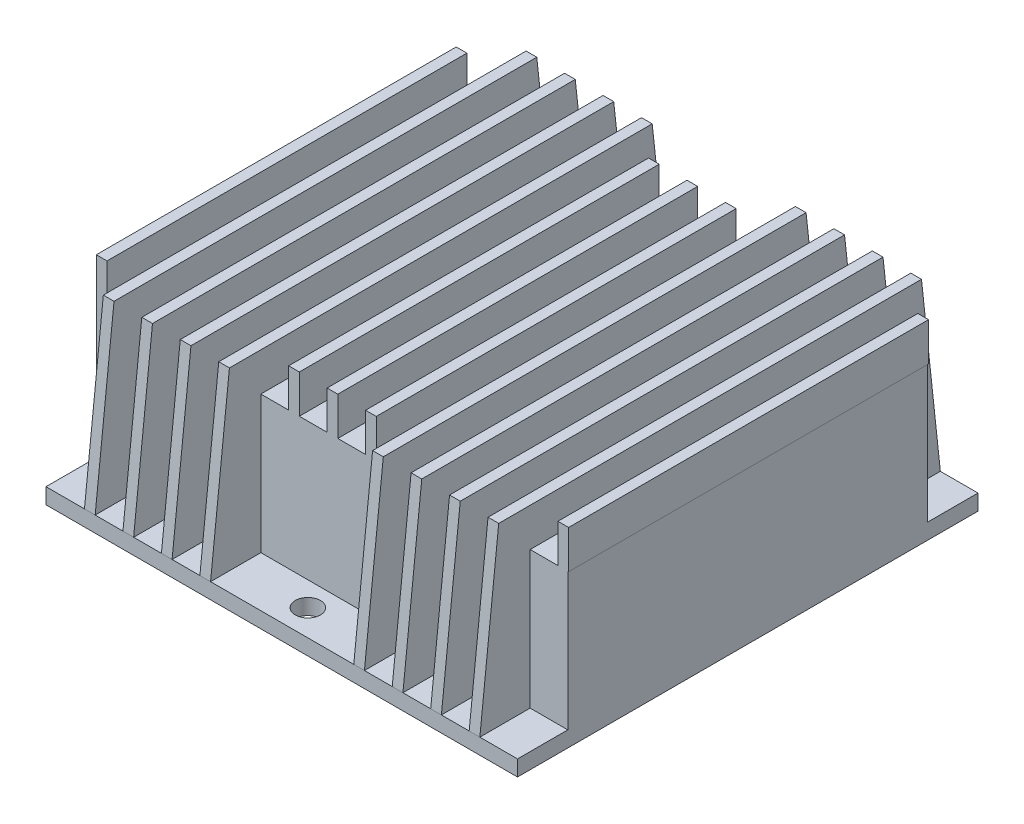
SolidWorks part; units mm, degrees
ref_plane "Front Plane" through (0, 0, 0) normal (0, 0, 1) x (1, 0, 0)
ref_plane "Top Plane" through (0, 0, 0) normal (0, 1, 0) x (1, 0, 0)
ref_plane "Right Plane" through (0, 0, 0) normal (1, 0, 0) x (0, 0, -1)
sketch "Sketch1" plane through (0, 0, 0) normal (0, 1, 0) x (1, 0, 0)
  line L1 (37.5, -36.625) -> (-37.5, -36.625)
  line L2 (37.5, -36.625) -> (37.5, 36.625)
  line L3 (37.5, 36.625) -> (-37.5, 36.625)
  line L4 (-37.5, -36.625) -> (-37.5, 36.625)
  line L5 (37.5, -36.625) -> (-37.5, 36.625) construction
  line L6 (37.5, 36.625) -> (-37.5, -36.625) construction
  point P0 (0, 0)
  dimension "D1" = 75
  dimension "D2" = 73.25
extrude "Boss-Extrude1" add sketch "Sketch1" along normal blind 2.5
sketch "Sketch2" plane through (0, 2.5, 0) normal (0, 1, 0) x (1, 0, 0)
  line L0 (-37.5, 36.625) -> (-37.5, -36.625) construction
  line L1 (37.5, -28.625) -> (-37.5, -28.625)
  line L2 (37.5, -28.625) -> (37.5, 28.625)
  line L3 (37.5, 28.625) -> (-37.5, 28.625)
  line L4 (-37.5, -28.625) -> (-37.5, 28.625)
  line L5 (37.5, -28.625) -> (-37.5, 28.625) construction
  line L6 (37.5, 28.625) -> (-37.5, -28.625) construction
  line L7 (37.5, 36.625) -> (-37.5, 36.625) construction
  point P0 (0, 0)
  dimension "D1" = 8
extrude "Boss-Extrude2" add sketch "Sketch2" along normal blind 21.85
sketch "Sketch3" plane through (-37.5, 0, 0) normal (-1, 0, 0) x (0, 0, 1)
  line L0 (-33.625, 30.45) -> (33.625, 30.45)
  line L1 (-28.625, 24.35) -> (28.625, 24.35) construction
  line L2 (-28.625, 24.35) -> (-28.625, 2.5) construction
  line L3 (28.625, 24.35) -> (28.625, 2.5) construction
  line L4 (-33.625, 30.45) -> (-36.625, 2.5)
  line L5 (-36.625, 2.5) -> (-28.625, 2.5)
  line L6 (-28.625, 2.5) -> (-28.625, 24.35)
  line L7 (-28.625, 24.35) -> (28.625, 24.35)
  line L8 (28.625, 24.35) -> (28.625, 2.5)
  line L9 (28.625, 2.5) -> (36.625, 2.5)
  line L10 (36.625, 2.5) -> (33.625, 30.45)
  dimension "D1" = 6.1
  dimension "D2" = 5
  dimension "D3" = 5
extrude "Boss-Extrude3" add sketch "Sketch3" against normal blind 1.7
pattern_linear "LPattern1" count 13 spacing 6.1192 along (1, 0, 0) of "Boss-Extrude3"
sketch "Sketch4" plane through (0, 24.35, 0) normal (0, 1, 0) x (1, 0, 0)
  line L1 (-35.8, -28.625) -> (-37.5, -28.625)
  line L2 (-35.8, -28.625) -> (-35.8, -36.625)
  line L3 (-35.8, -36.625) -> (-37.5, -36.625)
  line L4 (-37.5, -28.625) -> (-37.5, -36.625)
  line L9 (-5.2038, -36.625) -> (-0.7846, -36.625) construction
  line L10 (-6.9038, -28.625) -> (-5.2038, -28.625)
  line L11 (-6.9038, -28.625) -> (-6.9038, -36.625)
  line L12 (-6.9038, -36.625) -> (-5.2038, -36.625)
  line L13 (-5.2038, -28.625) -> (-5.2038, -36.625)
  line L14 (-5.2038, -28.625) -> (-5.2038, -36.625) construction
  line L16 (-0.7846, -28.625) -> (0.9154, -28.625)
  line L17 (-0.7846, -28.625) -> (-0.7846, -36.625)
  line L18 (-0.7846, -36.625) -> (0.9154, -36.625)
  line L19 (0.9154, -28.625) -> (0.9154, -36.625)
  line L20 (5.3346, -28.625) -> (7.0346, -28.625)
  line L21 (5.3346, -28.625) -> (5.3346, -36.625)
  line L22 (5.3346, -36.625) -> (7.0346, -36.625)
  line L23 (7.0346, -28.625) -> (7.0346, -36.625)
  line L24 (35.9308, -28.625) -> (37.6308, -28.625)
  line L25 (35.9308, -28.625) -> (35.9308, -36.625)
  line L26 (35.9308, -36.625) -> (37.6308, -36.625)
  line L27 (37.6308, -28.625) -> (37.6308, -36.625)
  line L28 (-37.5, 28.625) -> (-35.8, 28.625)
  line L29 (-37.5, 28.625) -> (-37.5, 36.625)
  line L30 (-37.5, 36.625) -> (-35.8, 36.625)
  line L31 (-35.8, 28.625) -> (-35.8, 36.625)
  line L32 (-6.9038, 28.625) -> (-5.2038, 28.625)
  line L33 (-6.9038, 28.625) -> (-6.9038, 36.625)
  line L34 (-6.9038, 36.625) -> (-5.2038, 36.625)
  line L35 (-5.2038, 28.625) -> (-5.2038, 36.625)
  line L42 (5.3346, 28.625) -> (7.0346, 28.625)
  line L43 (5.3346, 28.625) -> (5.3346, 36.625)
  line L44 (5.3346, 36.625) -> (7.0346, 36.625)
  line L45 (7.0346, 28.625) -> (7.0346, 36.625)
  line L46 (35.9308, 28.625) -> (37.6308, 28.625)
  line L47 (35.9308, 28.625) -> (35.9308, 36.625)
  line L48 (35.9308, 36.625) -> (37.6308, 36.625)
  line L49 (37.6308, 28.625) -> (37.6308, 36.625)
  line L50 (-0.7846, 36.625) -> (0.9154, 36.625)
  line L51 (-0.7846, 36.625) -> (-0.7846, 28.625)
  line L52 (-0.7846, 28.625) -> (0.9154, 28.625)
  line L53 (0.9154, 36.625) -> (0.9154, 28.625)
extrude "Cut-Extrude1" cut sketch "Sketch4" against normal up to surface and the other way up to surface up to face at (33.7212, 2.5, -32.625) other way up to face at (36.7808, 30.45, 0)
sketch "Sketch5" plane through (0, 2.5, 0) normal (0, 1, 0) x (1, 0, 0)
  line L2 (0, 32.475) -> (0, -32.475) construction
  circle A0 centre (0, 32.475) radius 2
  circle A1 centre (0, -32.475) radius 2
  point P6 (0, 0)
  dimension "D1" = 4
  dimension "D2" = 64.95
extrude "Cut-Extrude2" cut sketch "Sketch5" against normal through all
sketch "Sketch6" plane through (-37.5, 0, 0) normal (-1, 0, 0) x (0, 0, 1)
  line L0 (-36.625, 0) -> (36.625, 0) construction
  line L1 (-15.8, 0) -> (15.8, 0)
  line L2 (-15.8, 0) -> (-15.8, 16.5)
  line L3 (-15.8, 16.5) -> (15.8, 16.5)
  line L4 (15.8, 0) -> (15.8, 16.5)
  point P6 (0, 0)
  dimension "D1" = 16.5
  dimension "D2" = 31.6
extrude "Boss-Extrude4" add sketch "Sketch6" along normal blind 2.5
equation "\"D3@LPattern1\"=75/12-1.7/13"
